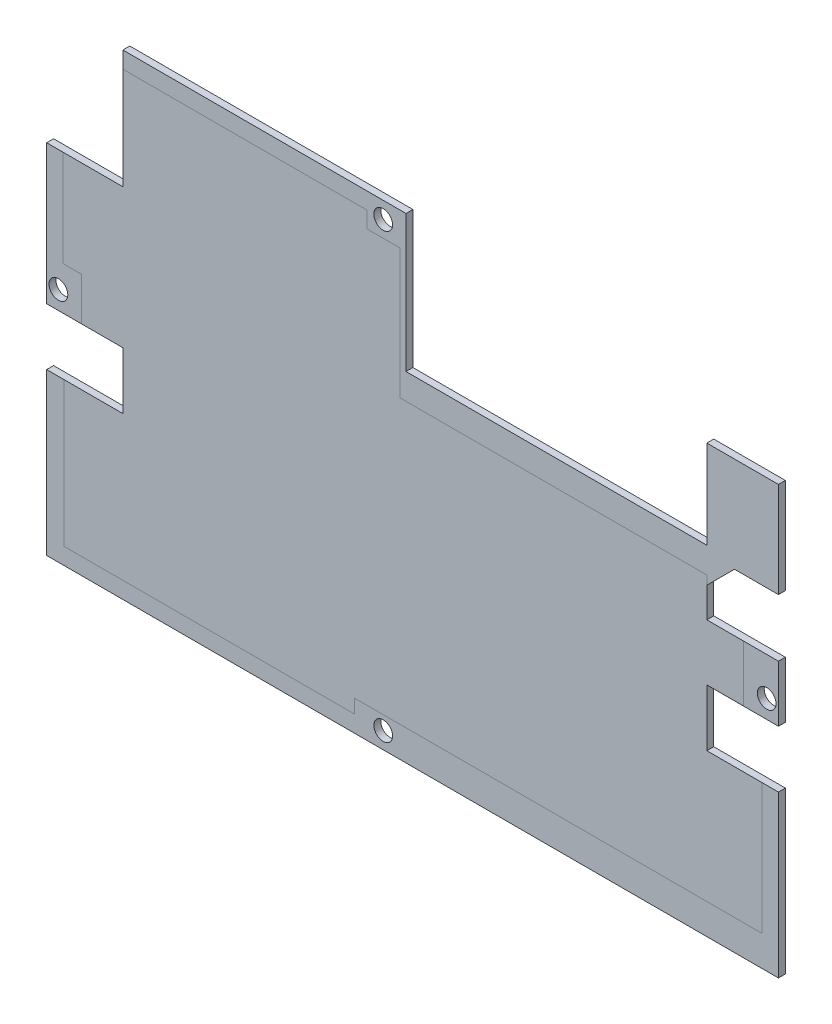
SolidWorks part; units mm, degrees
ref_plane "Front Plane" through (0, 0, 0) normal (0, 0, 1) x (1, 0, 0)
ref_plane "Top Plane" through (0, 0, 0) normal (0, 1, 0) x (1, 0, 0)
ref_plane "Right Plane" through (0, 0, 0) normal (1, 0, 0) x (0, 0, -1)
sketch "Sketch1" plane through (0, 0, 0) normal (0, 0, 1) x (1, 0, 0)
  line L0 (9.878, 12.192) -> (9.878, -93.472) construction
  line L1 (-41.367, 14.097) -> (6.6634, 14.097)
  line L2 (-41.367, 14.097) -> (-41.367, -13.0805)
  line L3 (-38.029, -95.123) -> (9.878, -95.123)
  line L4 (91.388, 14.5) -> (91.388, -20.5) construction
  line L5 (-41.367, 14.097) -> (9.878, -95.123) construction
  line L6 (-38.029, -95.123) -> (6.6634, 14.097) construction
  line L8 (-38.029, -95.123) -> (-58.8607, -95.123)
  line L10 (-41.367, -58.1655) -> (-58.8607, -58.1655)
  line L11 (-58.8607, -95.123) -> (-58.8607, -58.1655)
  line L12 (-38.029, -95.123) -> (-58.8607, -58.1655) construction
  line L13 (-41.367, -58.1655) -> (-58.8607, -95.123) construction
  line L14 (9.878, -95.123) -> (90.0829, -95.123)
  line L15 (99.008, -18.923) -> (109.0968, -18.923)
  line L16 (23.618, -17.32) -> (92.658, -17.32)
  line L17 (92.658, -58.1655) -> (92.658, -45.0855)
  line L18 (9.878, -95.123) -> (92.658, -17.32) construction
  line L19 (7.5194, -20.856) -> (90.0829, -95.123) construction
  line L20 (24.888, -20.5) -> (24.888, 14.5) construction
  line L21 (6.6634, 14.097) -> (23.618, 14.097)
  line L22 (92.658, -17.32) -> (92.658, 2.9845)
  line L23 (92.658, 2.9845) -> (109.0968, 2.9845)
  line L24 (23.618, 14.097) -> (23.618, -17.32)
  line L25 (6.6634, 14.097) -> (23.618, -17.32) construction
  line L26 (6.8209, -14.9887) -> (23.618, 14.097) construction
  line L27 (109.0968, -18.923) -> (109.0968, 2.9845)
  line L28 (90.0829, -95.123) -> (109.0968, -95.123)
  line L29 (92.658, -10.8044) -> (109.0968, 2.9845) construction
  line L30 (92.658, -58.1655) -> (109.0968, -58.1655)
  line L31 (109.0968, -95.123) -> (109.0968, -58.1655)
  line L32 (90.0829, -95.123) -> (109.0968, -58.1655) construction
  line L33 (92.658, -58.1655) -> (109.0968, -95.123) construction
  line L34 (92.658, 2.9845) -> (109.0968, -18.923) construction
  line L35 (99.008, -18.923) -> (92.658, -25.273)
  line L36 (89.888, -16.05) -> (26.388, -16.05) construction
  line L38 (-58.8607, -13.0805) -> (-41.367, -13.0805)
  line L39 (-58.8607, -13.0805) -> (-58.8607, -45.0855)
  line L40 (-58.8607, -45.0855) -> (-41.367, -45.0855)
  line L42 (-58.8607, -13.0805) -> (-41.367, -45.0855) construction
  line L43 (-58.8607, -45.0855) -> (-41.367, -13.0805) construction
  line L44 (-41.367, -45.0855) -> (-41.367, -58.1655)
  line L45 (111.6368, -97.663) -> (-61.4007, -97.663) construction
  line L46 (-44.732, 16.637) -> (94.968, 16.637) construction
  line L47 (-43.907, -8.6021) -> (-43.907, -4.4789) construction
  line L48 (-45.8454, -10.5405) -> (-49.9686, -10.5405) construction
  line L49 (-61.4007, -97.663) -> (-61.4007, 5.5245) construction
  line L50 (-45.8454, -47.6255) -> (-49.9686, -47.6255) construction
  line L51 (-45.8454, -55.6255) -> (-49.9686, -55.6255) construction
  line L52 (100.048, 5.5245) -> (111.6368, 5.5245) construction
  line L53 (111.6368, 5.5245) -> (111.6368, -97.663) construction
  line L54 (101.4746, -55.6255) -> (97.3514, -55.6255) construction
  line L55 (101.4746, -47.6255) -> (97.3514, -47.6255) construction
  line L56 (92.658, -32.1509) -> (109.0968, -32.1509)
  line L58 (92.658, -45.0855) -> (109.0968, -45.0855)
  line L59 (109.0968, -32.1509) -> (109.0968, -45.0855)
  line L60 (92.658, -32.1509) -> (109.0968, -45.0855) construction
  line L61 (92.658, -45.0855) -> (109.0968, -32.1509) construction
  line L62 (92.658, -32.1509) -> (92.658, -25.273)
  point P4 (-15.7115, -40.5833)
  point P12 (-49.352, -75.0348)
  point P17 (49.1005, -58.2587)
  point P26 (14.8536, -1.0794)
  point P32 (100.2804, -75.3021)
  point P38 (99.008, -5.478)
  point P52 (-50.1139, -29.083)
  point P76 (100.8774, -38.6182)
  dimension "D4" = 45
  dimension "D1" = 1.27
  dimension "D2" = 1.27
  dimension "D5" = 1.27
  dimension "D6" = 2.54
  dimension "D7" = 2.54
  dimension "D8" = 2.54
  dimension "D9" = 2.54
  dimension "D10" = 2.54
  dimension "D11" = 2.54
  dimension "D12" = 2.54
  dimension "D13" = 2.54
  dimension "D14" = 2.54
  dimension "D15" = 2.54
  dimension "D17" = 2.54
  dimension "D18" = 2.54
  dimension "D19" = 6.35
extrude "Boss-Extrude1" add sketch "Sketch1" along normal blind 1.5875 contours L1 L21 L24 L16 L22 L23 L27 L15 L35 L62 L56 L59 L58 L17 L30 L31 L28 L14 L3 L8 L11 L10 L44 L40 L39 L38 L2
hole_wizard "#6 Clearance Hole1" positions "Sketch3" profile "Sketch2" hole size "#6" standard "ANSI Inch" end condition through all
sketch "Sketch3" plane through (0, 0, 0) normal (0, 0, -1) x (-1, 0, 0)
  point P0 (-106.398, -40.894)
  point P2 (-18.387, 10.287)
  point P4 (56.162, -40.894)
  point P6 (-18.387, -91.313)
sketch "Sketch2" plane through (106.398, -40.894, 0) normal (1, 0, 0) x (0, 1, 0)
  line L0 (0, 0) -> (0, 1.5875)
  line L1 (0, 1.5875) -> (2.1526, 1.5875)
  line L2 (2.1526, 1.5875) -> (2.1526, 0)
  line L5 (2.1526, 0) -> (0, 0)
  line L11 (0, -6.35) -> (0, 107.95) construction
  dimension "Thru Hole Dia." = 4.3053
  dimension "Thru Hole Depth" = 1.5875
sketch "Sketch4" plane through (0, 0, 1.5875) normal (0, 0, 1) x (1, 0, 0)
  line L0 (-41.367, 10.287) -> (14.6198, 10.287)
  line L1 (-41.367, 14.097) -> (-41.367, -13.0805) construction
  line L2 (14.6198, 10.287) -> (14.6198, 6.5468)
  line L3 (14.6198, 6.5468) -> (22.2764, 6.5468)
  line L4 (22.2764, 6.5468) -> (22.2764, -23.243)
  line L5 (22.2764, -23.243) -> (92.7226, -23.243)
  line L6 (92.7226, -23.243) -> (92.658, -32.1509)
  line L7 (92.658, -32.1509) -> (101.0599, -32.1509)
  line L8 (101.0599, -32.1509) -> (101.0599, -45.0385)
  line L9 (101.0599, -45.0385) -> (92.658, -45.0855)
  line L10 (92.658, -45.0855) -> (92.658, -58.1655)
  line L11 (92.658, -58.1655) -> (105.3245, -58.1655)
  line L12 (105.3245, -58.1655) -> (105.2868, -88.138)
  line L13 (105.2868, -88.138) -> (11.7894, -88.138)
  line L14 (11.7894, -88.138) -> (11.7894, -91.313)
  line L15 (11.7894, -91.313) -> (-54.9021, -91.313)
  line L16 (-54.9021, -91.313) -> (-54.9021, -58.1655)
  line L17 (-54.9021, -58.1655) -> (-41.367, -58.1655)
  line L18 (-41.367, -58.1655) -> (-41.367, -45.0855)
  line L19 (-41.367, -45.0855) -> (-50.8981, -45.0855)
  line L20 (-50.8981, -45.0855) -> (-50.8981, -35.2241)
  line L21 (-50.8981, -35.2241) -> (-55.1233, -35.2241)
  line L22 (-55.1233, -35.2241) -> (-55.1233, -13.0805)
  line L23 (-55.1233, -13.0805) -> (-41.367, -13.0805)
  line L24 (-41.367, -13.0805) -> (-41.367, 10.287)
  point P30 (11.7894, -91.313)
split line "Split Line1"
